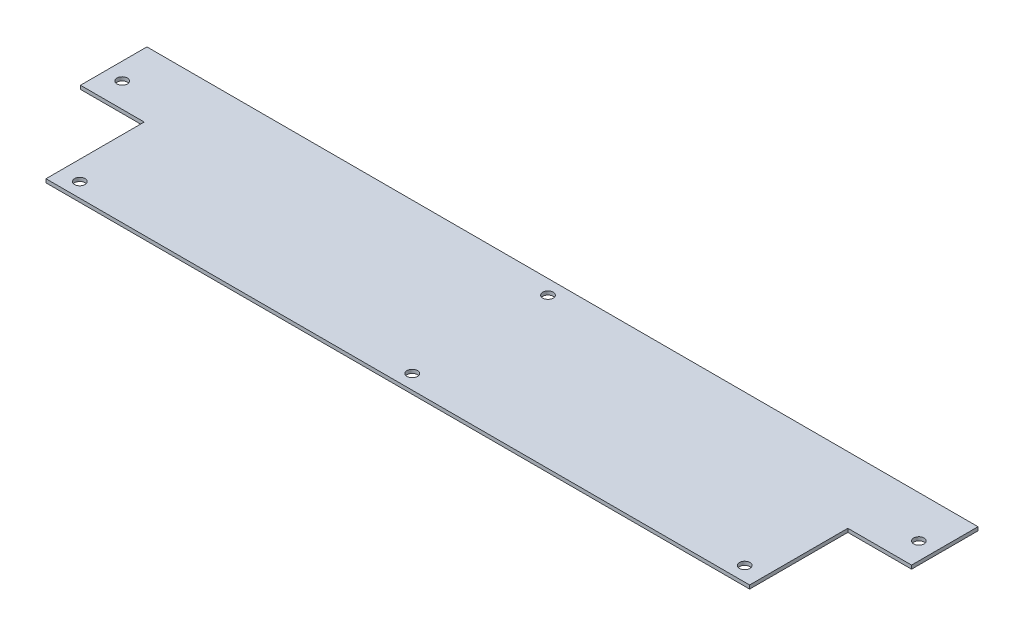
SolidWorks part; units mm, degrees
ref_plane "Front Plane" through (0, 0, 0) normal (0, 0, 1) x (1, 0, 0)
ref_plane "Top Plane" through (0, 0, 0) normal (0, 1, 0) x (1, 0, 0)
ref_plane "Right Plane" through (0, 0, 0) normal (1, 0, 0) x (0, 0, -1)
sketch "Sketch1" plane through (0, 0, 0) normal (0, 1, 0) x (1, 0, 0)
  line L0 (0, 0) -> (0, -29.845) construction
  line L1 (190.5, -36.195) -> (-190.5, -36.195) construction
  line L2 (190.5, -36.195) -> (190.5, 36.195) construction
  line L3 (190.5, 36.195) -> (-190.5, 36.195) construction
  line L4 (-190.5, -36.195) -> (-190.5, 36.195) construction
  line L5 (190.5, -36.195) -> (-190.5, 36.195) construction
  line L6 (190.5, 36.195) -> (-190.5, -36.195) construction
  line L7 (-146.177, -29.845) -> (146.177, -29.845) construction
  line L8 (0, 0) -> (0, 29.845) construction
  line L27 (0, 0) -> (0, 17.78) construction
  line L34 (-175.1457, 17.78) -> (175.1457, 17.78) construction
  line L35 (-154.686, -36.195) -> (-154.686, 6.985)
  line L48 (154.686, -36.195) -> (154.686, 6.985)
  line L49 (154.686, -36.195) -> (-154.686, -36.195)
  line L50 (-154.686, 6.985) -> (-182.7083, 6.985)
  line L52 (-182.7083, 36.195) -> (-182.7083, 6.985)
  line L53 (-182.7083, 36.195) -> (182.7083, 36.195)
  line L54 (182.7083, 36.195) -> (182.7083, 6.985)
  line L55 (182.7083, 6.985) -> (154.686, 6.985)
  circle A0 centre (175.1457, 17.78) radius 2.286
  circle A1 centre (0, 29.845) radius 2.286
  circle A2 centre (146.177, -29.845) radius 2.286
  circle A3 centre (-175.1457, 17.78) radius 2.286
  circle A4 centre (0, -29.845) radius 2.286
  circle A5 centre (-146.177, -29.845) radius 2.286
  point P0 (0, 0)
  point P10 (0, -29.845)
  point P21 (0, 36.195)
  point P22 (0, -36.195)
  point P58 (0, 17.78)
  dimension "D5" = 4.572
  dimension "D1" = 381
  dimension "D2" = 72.39
  dimension "D4" = 292.354
  dimension "D6" = 29.845
  dimension "D7" = 17.78
  dimension "D8" = 350.2914
  dimension "D9" = 309.372
  dimension "D10" = 6.35
  dimension "D11" = 43.18
  dimension "D12" = 43.18
  dimension "D13" = 28.0223
  dimension "D14" = 175.1457
  dimension "D15" = 175.1457
  dimension "D16" = 182.7083
  dimension "D17" = 182.7083
extrude "Boss-Extrude1" add sketch "Sketch1" along normal blind 1.5875
